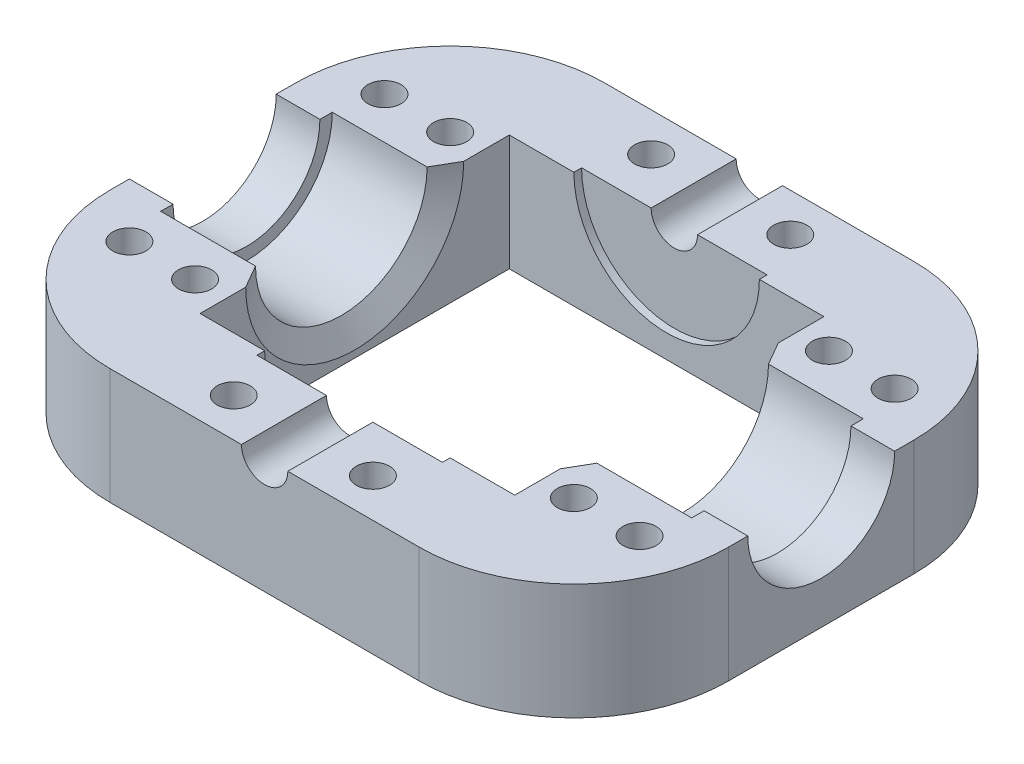
SolidWorks part; units mm, degrees
ref_plane "Спереди" through (0, 0, 0) normal (0, 0, 1) x (1, 0, 0)
ref_plane "Сверху" through (0, 0, 0) normal (0, 1, 0) x (1, 0, 0)
ref_plane "Справа" through (0, 0, 0) normal (1, 0, 0) x (0, 0, -1)
sketch "Sketch1" plane through (0, 0, 0) normal (0, 1, 0) x (1, 0, 0)
  line L1 (40, -32) -> (-40, -32)
  line L2 (40, -32) -> (40, 32)
  line L3 (40, 32) -> (-40, 32)
  line L4 (-40, -32) -> (-40, 32)
  line L5 (40, -32) -> (-40, 32) construction
  line L6 (40, 32) -> (-40, -32) construction
  line L7 (20.35, -20) -> (-20.35, -20)
  line L8 (20.35, -20) -> (20.35, 20)
  line L9 (20.35, 20) -> (-20.35, 20)
  line L10 (-20.35, -20) -> (-20.35, 20)
  line L11 (20.35, -20) -> (-20.35, 20) construction
  line L12 (20.35, 20) -> (-20.35, -20) construction
  point P0 (0, 0)
  point P6 (0, 0)
  dimension "D1" = 80
  dimension "D2" = 64
  dimension "D3" = 40
  dimension "D4" = 40.7
extrude "Boss-Extrude1" add sketch "Sketch1" along normal blind 15
sketch "Sketch3" plane through (0, 15, 0) normal (0, 1, 0) x (1, 0, 0)
  line L0 (-20.35, 0) -> (-40, 0) construction
  line L1 (-20.35, 20) -> (-20.35, -20) construction
  line L2 (-40, 32) -> (-40, -32) construction
  line L3 (20.35, 0) -> (40, 0) construction
  line L4 (20.35, -20) -> (20.35, 20) construction
  line L5 (40, -32) -> (40, 32) construction
  line L10 (20.35, -11.1) -> (34.35, -11.1)
  line L11 (20.35, -11.1) -> (20.35, 0)
  line L12 (20.35, 0) -> (34.35, 0)
  line L13 (34.35, -11.1) -> (34.35, 0)
  line L14 (20.35, -11.1) -> (34.35, 0) construction
  line L15 (20.35, 0) -> (34.35, -11.1) construction
  line L16 (-34.35, -11.1) -> (-20.35, -11.1)
  line L17 (-34.35, -11.1) -> (-34.35, 0)
  line L18 (-34.35, 0) -> (-20.35, 0)
  line L19 (-20.35, -11.1) -> (-20.35, 0)
  line L20 (-34.35, -11.1) -> (-20.35, 0) construction
  line L21 (-34.35, 0) -> (-20.35, -11.1) construction
  point P18 (27.35, -5.55)
  point P23 (-27.35, -5.55)
  dimension "D1" = 14
  dimension "D2" = 11.1
revolve "Cut-Revolve1" cut sketch "Sketch3" angle 360 about L12
sketch "Sketch4" plane through (40, 0, 0) normal (1, 0, 0) x (0, 0, -1)
  line L0 (-32, 15) -> (32, 15) construction
  circle A0 centre (0, 15) radius 9.5
  dimension "D1" = 19
extrude "Cut-Extrude2" cut sketch "Sketch4" against normal through all
sketch "Sketch5" plane through (0, 0, 32) normal (0, 0, 1) x (1, 0, 0)
  line L0 (-40, 15) -> (40, 15) construction
  circle A0 centre (0, 15) radius 3
  dimension "D1" = 6
extrude "Cut-Extrude3" cut sketch "Sketch5" against normal through all
sketch "Sketch8" plane through (0, 15, 0) normal (0, 1, 0) x (1, 0, 0)
  line L1 (-24.5, -16.5) -> (24.5, -16.5) construction
  line L2 (-24.5, -16.5) -> (-24.5, 16.5) construction
  line L3 (-24.5, 16.5) -> (24.5, 16.5) construction
  line L4 (24.5, -16.5) -> (24.5, 16.5) construction
  line L5 (-24.5, -16.5) -> (24.5, 16.5) construction
  line L6 (-24.5, 16.5) -> (24.5, -16.5) construction
  line L7 (-9, 27) -> (9, 27) construction
  line L8 (-9, 27) -> (-9, -27) construction
  line L9 (-9, -27) -> (9, -27) construction
  line L10 (9, 27) -> (9, -27) construction
  line L11 (-9, 27) -> (9, -27) construction
  line L12 (-9, -27) -> (9, 27) construction
  line L13 (33, -16.5) -> (-33, -16.5) construction
  line L14 (33, -16.5) -> (33, 16.5) construction
  line L15 (33, 16.5) -> (-33, 16.5) construction
  line L16 (-33, -16.5) -> (-33, 16.5) construction
  line L17 (33, -16.5) -> (-33, 16.5) construction
  line L18 (33, 16.5) -> (-33, -16.5) construction
  circle A0 centre (24.5, 16.5) radius 2.15
  circle A1 centre (24.5, -16.5) radius 2.15
  circle A2 centre (-24.5, -16.5) radius 2.15
  circle A3 centre (-24.5, 16.5) radius 2.15
  circle A4 centre (9, -27) radius 2.15
  circle A5 centre (-9, -27) radius 2.15
  circle A6 centre (-9, 27) radius 2.15
  circle A7 centre (9, 27) radius 2.15
  circle A8 centre (-33, 16.5) radius 2.15
  circle A9 centre (33, 16.5) radius 2.15
  circle A10 centre (33, -16.5) radius 2.15
  circle A11 centre (-33, -16.5) radius 2.15
  circle A12 centre (-24.5, 16.5) radius 4 construction
  circle A13 centre (-33, 16.5) radius 4 construction
  point P0 (0, 0)
  point P10 (0, 0)
  point P16 (0, 0)
  dimension "D3" = 4.3
  dimension "D7" = 8
  dimension "D1" = 33
  dimension "D2" = 49
  dimension "D4" = 18
  dimension "D5" = 54
  dimension "D6" = 66
extrude "Cut-Extrude6" cut sketch "Sketch8" against normal through all
fillet "Fillet1" radius 20 4 edges at (-40, 7.5, 32) (-40, 7.5, -32) (40, 7.5, -32) (40, 7.5, 32)
chamfer "Chamfer1" distance 3 angle 30 2 edges at (-20.35, 3.9, 0) (20.35, 3.9, 0) first distance on face at (-20.35, 8.15, 0) first distance on face at (20.35, 8.15, 0)
sketch "Sketch9" plane through (0, 15, 0) normal (0, 1, 0) x (1, 0, 0)
  line L0 (0, 29.8714) -> (0, -31.0419) construction
  line L1 (-3, 20) -> (-20.35, 20) construction
  line L2 (-12, -21) -> (0, -21)
  line L3 (-12, -21) -> (-12, -20)
  line L4 (-12, -20) -> (0, -20)
  line L5 (0, -21) -> (0, -20)
  line L6 (-12, -21) -> (0, -20) construction
  line L7 (-12, -20) -> (0, -21) construction
  line L8 (-12, 20) -> (0, 20)
  line L9 (-12, 20) -> (-12, 21)
  line L10 (-12, 21) -> (0, 21)
  line L11 (0, 20) -> (0, 21)
  line L12 (-12, 20) -> (0, 21) construction
  line L13 (-12, 21) -> (0, 20) construction
  line L14 (-20.35, -20) -> (-3, -20) construction
  point P3 (-6, -20.5)
  point P8 (-6, 20.5)
  dimension "D1" = 1
  dimension "D2" = 12
revolve "Cut-Revolve2" cut sketch "Sketch9" angle 360 about L0
